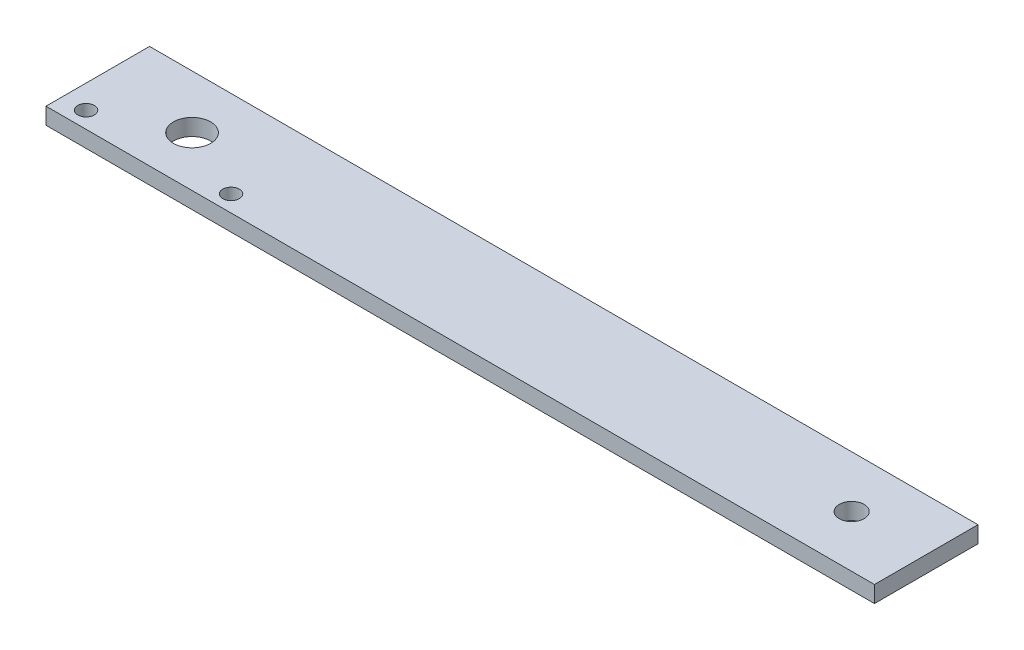
SolidWorks part; units mm, degrees
ref_plane "Front Plane" through (0, 0, 0) normal (0, 0, 1) x (1, 0, 0)
ref_plane "Top Plane" through (0, 0, 0) normal (0, 1, 0) x (1, 0, 0)
ref_plane "Right Plane" through (0, 0, 0) normal (1, 0, 0) x (0, 0, -1)
sketch "Sketch1" plane through (0, 0, 0) normal (0, 1, 0) x (1, 0, 0)
  line L1 (-100, 12.5) -> (100, 12.5)
  line L2 (-100, 12.5) -> (-100, -12.5)
  line L3 (-100, -12.5) -> (100, -12.5)
  line L4 (100, 12.5) -> (100, -12.5)
  line L5 (-100, 12.5) -> (100, -12.5) construction
  line L6 (-100, -12.5) -> (100, 12.5) construction
  circle A0 centre (-76.8416, -0.4014) radius 4.5
  circle A1 centre (-76.82, -7.4013) radius 14
  circle A2 centre (-94.32, -8.5039) radius 2
  circle A3 centre (-59.32, -8.5039) radius 2
  circle A4 centre (82, 0) radius 3
  point P0 (0, 0)
  point P17 (100, 0)
  dimension "D3" = 18
  dimension "D1" = 25
  dimension "D2" = 200
extrude "Boss-Extrude1" add sketch "Sketch1" along normal blind 4 contours A1 L3 L4 L1 L2 A4 A3 A2 | L3 A1 A0 region at (7.5531, 0, -0.4551) region at (-79.3515, 0, -6.0232)
